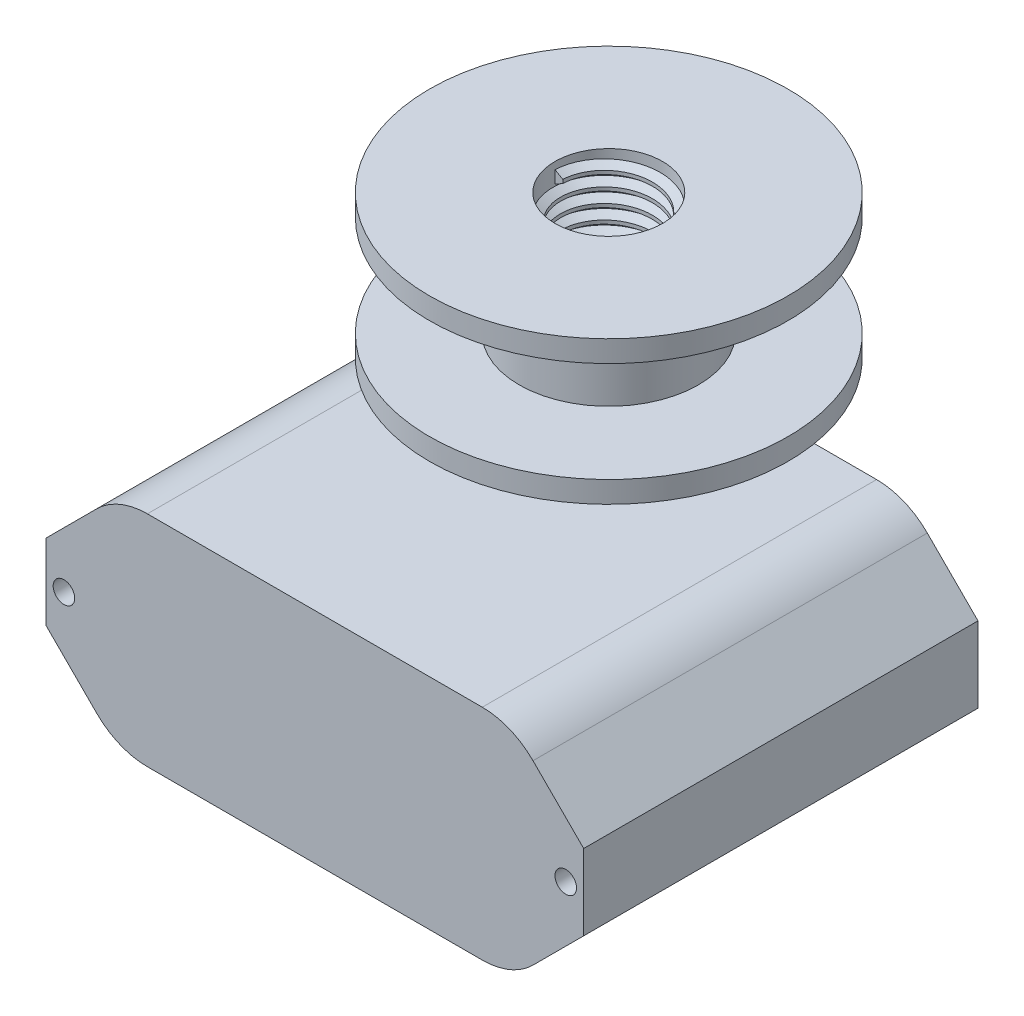
SolidWorks part; units mm, degrees
material "PA Tipo 6"
ref_plane "Front Plane" through (0, 0, 0) normal (0, 0, 1) x (1, 0, 0)
ref_plane "Top Plane" through (0, 0, 0) normal (0, 1, 0) x (1, 0, 0)
ref_plane "Right Plane" through (0, 0, 0) normal (1, 0, 0) x (0, 0, -1)
sketch "Croquis1" plane through (0, 0, 0) normal (0, 0, 1) x (1, 0, 0)
  line L1 (37.5, -15.276) -> (-37.5, -15.276)
  line L2 (37.5, -15.276) -> (37.5, 15.276)
  line L3 (37.5, 15.276) -> (-37.5, 15.276)
  line L4 (-37.5, -15.276) -> (-37.5, 15.276)
  line L5 (37.5, -15.276) -> (-37.5, 15.276) construction
  line L6 (37.5, 15.276) -> (-37.5, -15.276) construction
  point P0 (0, 0)
  dimension "D1" = 75
extrude "Saliente-Extruir1" add sketch "Croquis1" along normal blind 55
sketch "Croquis2" plane through (0, 0, 55) normal (0, 0, 1) x (1, 0, 0)
  line L0 (-37.5, 0) -> (-35, 0) construction
  line L1 (-37.5, 15.276) -> (-37.5, -15.276) construction
  line L2 (0, 38.2802) -> (0, -33.466) construction
  line L3 (37.5, 0) -> (35, 0) construction
  circle A0 centre (35, 0) radius 1.5
  circle A1 centre (-35, 0) radius 1.5
  dimension "D2" = 3
  dimension "D1" = 2.5
extrude "Cortar-Extruir1" cut sketch "Croquis2" against normal blind 55
sketch "Croquis3" plane through (0, 15.276, 0) normal (0, 1, 0) x (1, 0, 0)
  line L0 (0, 0) -> (0, -14) construction
  line L1 (37.5, 0) -> (-37.5, 0) construction
  circle A0 centre (0, -14) radius 10
  dimension "D2" = 20
  dimension "D1" = 14
extrude "Saliente-Extruir3" add sketch "Croquis3" along normal blind 10
sketch "Croquis4" plane through (0, 25.276, 0) normal (0, 1, 0) x (1, 0, 0)
  circle A0 centre (0, -14) radius 25
  dimension "D1" = 50
extrude "Saliente-Extruir4" add sketch "Croquis4" along normal blind 20
ref_plane "Plano1" through (0, 0, 14.01) normal (0, 0, -1) x (-1, 0, 0)
sketch "Croquis5" plane through (0, 0, 14.01) normal (0, 0, -1) x (-1, 0, 0)
  line L0 (0, 0) -> (0, 35.276) construction
  line L1 (25, 25.276) -> (25, 45.276) construction
  line L2 (12.5, 28.276) -> (37.5, 28.276)
  line L3 (12.5, 28.276) -> (12.5, 42.276)
  line L4 (12.5, 42.276) -> (37.5, 42.276)
  line L5 (37.5, 28.276) -> (37.5, 42.276)
  line L6 (12.5, 28.276) -> (37.5, 42.276) construction
  line L7 (12.5, 42.276) -> (37.5, 28.276) construction
  point P3 (25, 35.276)
  dimension "D1" = 14
  dimension "D2" = 25
sketch "Croquis7" plane through (0, 45.276, 0) normal (0, 1, 0) x (1, 0, 0)
  circle A0 centre (0, -14) radius 25
sweep "Cortar-Barrer1" cut profiles "Croquis5" path "Croquis7"
sketch "Croquis9" plane through (0, 45.276, 0) normal (0, 1, 0) x (1, 0, 0)
  line L0 (-25, -14) -> (0, -14) construction
  circle A0 centre (0, -14) radius 25 construction
hole_wizard "Taladro1" positions "Croquis3D3" profile "Croquis10" legacy
sketch3d "Croquis3D3"
  point P0 (0, 45.276, 14)
sketch "Croquis10" plane through (0, 45.276, 14) normal (1, 0, 0) x (0, 0, 1)
  line L0 (0, 0) -> (0, 35)
  line L1 (0, 35) -> (7.5, 35)
  line L2 (7.5, 35) -> (7.5, 0)
  line L3 (7.5, 0) -> (0, 0)
  line L4 (0, 110) -> (0, -10) construction
  dimension "Diámetro" = 15
  dimension "Profundidad" = 35
thread "Rosca1" pitch 2 method extrude profile "Perfil de rosca1" start angle 0, offset 1, length 35, pitch 2, diameter 15
ref_plane "Plano2" through (-7.5, 44.276, 14) normal (0, 0, 1) x (-1, 0, 0)
sketch "Perfil de rosca1" plane through (-7.5, 44.276, 14) normal (0, 0, 1) x (-1, 0, 0)
  line L0 (0, 0) -> (0, 2) construction
  line L11 (0, 0) -> (0, 1.75)
  line L12 (0, 1.75) -> (-1.0825, 1.125)
  line L13 (-1.0825, 1.125) -> (-1.0825, 0.625)
  line L15 (-1.0825, 0.625) -> (0, 0)
  line L17 (-1.0825, 0.875) -> (0, 0.875) construction
  point P2 (0, 0)
  dimension "Pitch" = 2
  dimension "Profile_Angle" = 60
  dimension "Profile_Land" = 0.5
  dimension "Profile_Height" = 1.0825
chamfer "Chaflán1" distance 10 angle 45 1 edges at (37.5, 15.276, 27.5)
chamfer "Chaflán2" distance 10 angle 45 1 edges at (-37.5, 15.276, 27.5)
fillet "Redondeo2" radius 10 1 edges at (-27.5, 15.276, 27.5)
fillet "Redondeo3" radius 10 1 edges at (27.5, 15.276, 27.5)
chamfer "Chaflán3" distance 10 angle 45 2 edges at (-37.5, -15.276, 27.5) (37.5, -15.276, 27.5)
fillet "Redondeo7" radius 10 2 edges at (27.5, -15.276, 27.5) (-27.5, -15.276, 27.5)
